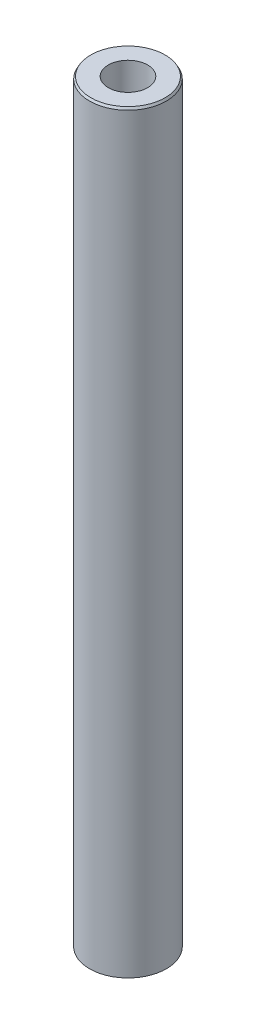
SolidWorks part; units mm, degrees
ref_plane "Front Plane" through (0, 0, 0) normal (0, 0, 1) x (1, 0, 0)
ref_plane "Top Plane" through (0, 0, 0) normal (0, 1, 0) x (1, 0, 0)
ref_plane "Right Plane" through (0, 0, 0) normal (1, 0, 0) x (0, 0, -1)
sketch "Sketch1" plane through (0, 0, 0) normal (0, 1, 0) x (1, 0, 0)
  circle A0 centre (0, 0) radius 7.5
  dimension "SHAFT_OD" = 15
extrude "Boss-Extrude1" add sketch "Sketch1" along normal blind 147.3627
sketch "Sketch2" plane through (0, 0, 0) normal (0, 1, 0) x (1, 0, 0)
  circle A0 centre (0, 0) radius 3.8463
  dimension "BORE_D" = 7.6927
extrude "Cut-Extrude1" cut sketch "Sketch2" along normal through all
chamfer "Chamfer1" distance 0.4367 angle 30 2 edges at (0, 147.3627, 7.5) (0, 0, 7.5) first distance on face at (0, 147.3627, 7.5) first distance on face at (0, 0, 3.8463)
